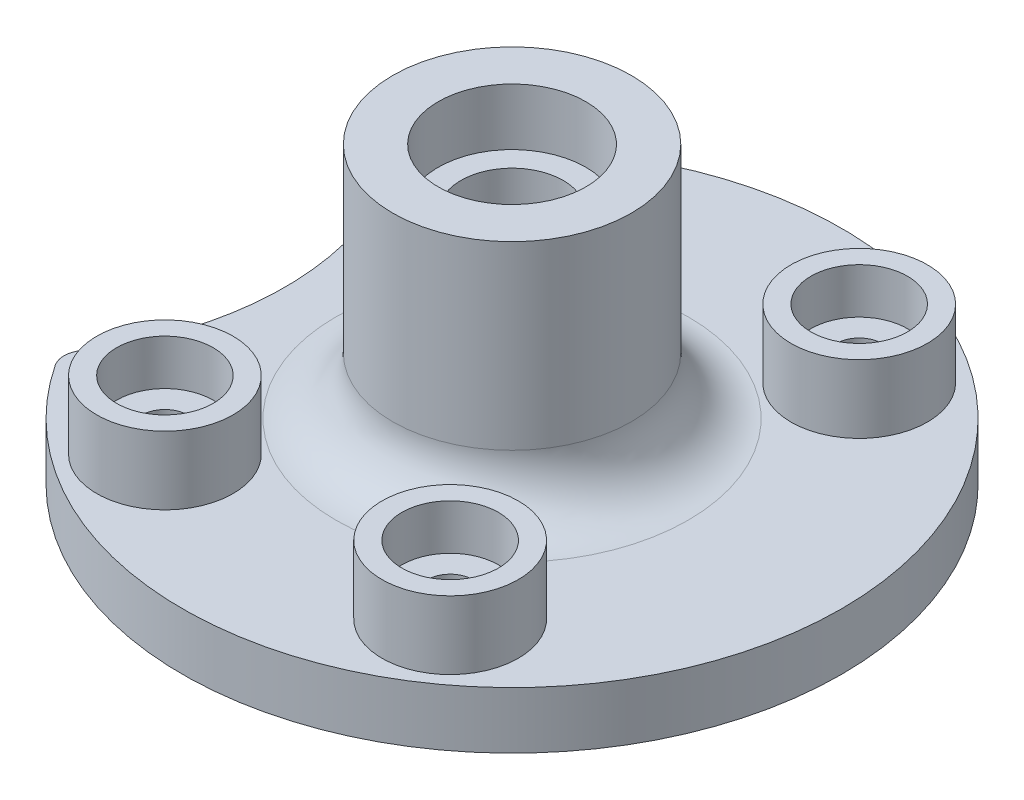
SolidWorks part; units mm, degrees
ref_plane "Plan de face" through (0, 0, 0) normal (0, 0, 1) x (1, 0, 0)
ref_plane "Plan de dessus" through (0, 0, 0) normal (0, 1, 0) x (1, 0, 0)
ref_plane "Plan de droite" through (0, 0, 0) normal (1, 0, 0) x (0, 0, -1)
sketch "Esquisse2" plane through (0, 0, 0) normal (1, 0, 0) x (0, 0, -1)
  line L2 (6.5, 5) -> (6.5, 10)
  line L3 (6.5, 10) -> (10.5, 10)
  line L4 (10.5, 10) -> (10.5, -10.9)
  line L5 (10.5, -10.9) -> (6.5, -10.9)
  line L6 (6.5, -10.9) -> (6.5, -5)
  line L9 (0, 0) -> (4.5, 0) construction
  line L11 (6.5, 5) -> (4.5, 5)
  line L12 (4.5, 5) -> (4.5, 0)
  line L14 (6.5, -5) -> (4.5, -5)
  line L15 (4.5, -5) -> (4.5, 0)
  line L16 (0, 0) -> (0, 6.6645) construction
  dimension "D2" = 5
  dimension "D3" = 5.9
  dimension "D4" = 4.5
  dimension "D5" = 6.5
  dimension "D8" = 5
  dimension "D9" = 5
  dimension "D10" = 4
revolve "Révolution1" add sketch "Esquisse2" angle 360 about L16
sketch "Esquisse3" plane through (0, -10.9, 0) normal (0, 1, 0) x (1, 0, 0)
  line L0 (0, 0) -> (-45, 0) construction
  circle A0 centre (0, 0) radius 6.5
  circle A2 centre (0, 0) radius 6.5 construction
  arc A4 (-24.9, 14.8657) -> (-24.9, -14.8657) centre (-45, 0) cw
  arc A5 (-24.9, 14.8657) -> (-24.9, -14.8657) centre (0, 0) cw
  dimension "D1" = 29
  dimension "D3" = 25
  dimension "D2" = 45
extrude "Boss.-Extru.1" add sketch "Esquisse3" against normal blind 5
fillet "Congé1" radius 5 1 edges at (0, -10.9, -10.5)
sketch "Esquisse5" plane through (0, -10.9, 0) normal (0, 1, 0) x (1, 0, 0)
  line L0 (0, 0) -> (-34, 0) construction
  line L1 (-34, 0) -> (-12.5508, 17.9981) construction
  circle A0 centre (-12.5508, 17.9981) radius 6
  circle A1 centre (-12.5508, 17.9981) radius 4.25
  circle A2 centre (-12.5508, -17.9981) radius 4.25
  circle A3 centre (-12.5508, -17.9981) radius 6
  dimension "D4" = 8.5
  dimension "D5" = 12
  dimension "D1" = 34
  dimension "D2" = 40
  dimension "D3" = 28
extrude "Boss.-Extru.3" add sketch "Esquisse5" along normal blind 6
sketch "Esquisse8" plane through (0, -10.9, 0) normal (0, 1, 0) x (1, 0, 0)
  circle A0 centre (-12.5508, -17.9981) radius 4.25
  circle A1 centre (-12.5508, -17.9981) radius 4.25 construction
  circle A2 centre (-12.5508, 17.9981) radius 4.25
  circle A3 centre (-12.5508, 17.9981) radius 4.25 construction
extrude "Boss.-Extru.4" add sketch "Esquisse8" along normal blind 2
sketch "Esquisse6" plane through (0, -10.9, 0) normal (0, 1, 0) x (1, 0, 0)
  circle A0 centre (-12.5508, -17.9981) radius 2
  circle A1 centre (-12.5508, 17.9981) radius 2
  dimension "D1" = 4
  dimension "D2" = 4
extrude "Enlèv. mat.-Extru.1" cut sketch "Esquisse6" against normal through all both and the other way through all
sketch "Esquisse7" plane through (0, -15.9, 0) normal (0, -1, 0) x (1, 0, 0)
  circle A0 centre (-12.5508, 17.9981) radius 3
  circle A1 centre (-12.5508, -17.9981) radius 3
  dimension "D1" = 6
  dimension "D2" = 6
extrude "Enlèv. mat.-Extru.2" cut sketch "Esquisse7" against normal blind 3
fillet "Congé2" radius 2 2 edges at (-24.9, -13.4, 14.8657) (-24.9, -13.4, -14.8657)
mirror "Symétrie1" about plane through (0, 0, 0) normal (1, 0, 0) of "Enlèv. mat.-Extru.2", "Enlèv. mat.-Extru.1", "Boss.-Extru.4", "Boss.-Extru.3"
